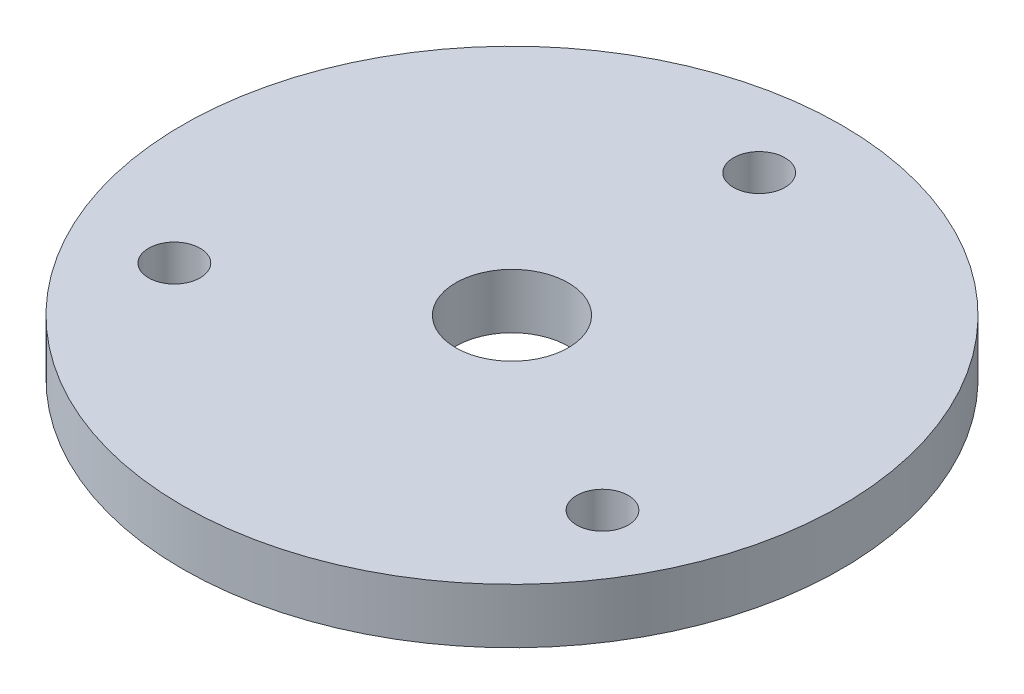
SolidWorks part; units mm, degrees
ref_plane "Front Plane" through (0, 0, 0) normal (0, 0, 1) x (1, 0, 0)
ref_plane "Top Plane" through (0, 0, 0) normal (0, 1, 0) x (1, 0, 0)
ref_plane "Right Plane" through (0, 0, 0) normal (1, 0, 0) x (0, 0, -1)
sketch "Sketch1" plane through (0, 0, 0) normal (0, 0, 1) x (1, 0, 0)
  line L1 (-76.2, 0) -> (76.2, 0) construction
  dimension "OD" = 152.4
sketch "Sketch2" plane through (0, 0, 0) normal (0, 0, 1) x (1, 0, 0)
  line L0 (0, -6.35) -> (0, 6.35)
  point P4 (0, 0)
  dimension "Thickness" = 12.7
sketch "Sketch3" plane through (0, 0, 0) normal (0, 1, 0) x (1, 0, 0)
  circle A0 centre (0, 0) radius 76.2
extrude "Boss-Extrude1" add sketch "Sketch3" along normal up to vertex (6.35 mm away) and the other way up to vertex (6.35 mm away) up to point (0, 6.35, 0) other way up to point (0, -6.35, 0)
sketch "Sketch4" plane through (0, 6.35, 0) normal (0, 1, 0) x (1, 0, 0)
  circle A0 centre (0, 0) radius 13.0175
  circle A1 centre (0, 0) radius 57.15 construction
  circle A2 centre (0, 57.15) radius 5.9531
  circle A3 centre (49.4934, -28.575) radius 5.9531
  circle A4 centre (-49.4934, -28.575) radius 5.9531
  point P13 (0, 0)
  dimension "D1" = 26.035
  dimension "D2" = 114.3
  dimension "D3" = 11.9062
  dimension "D4" = 3
extrude "Cut-Extrude1" cut sketch "Sketch4" against normal through all
